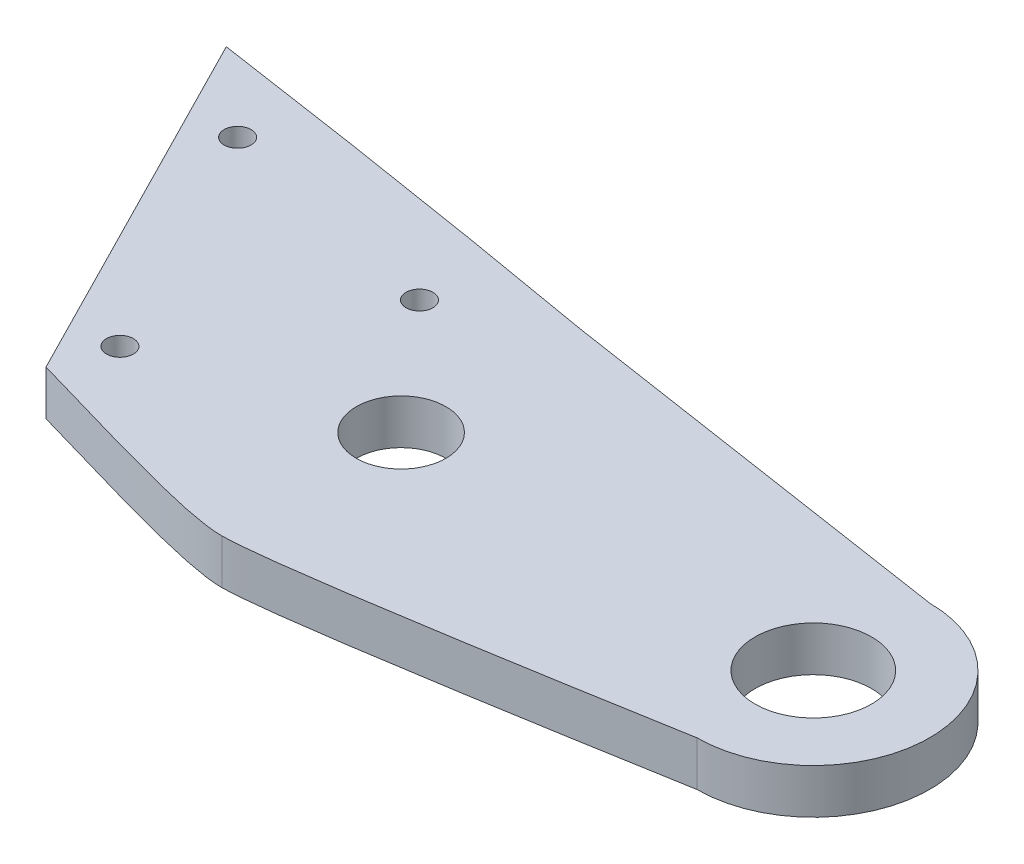
SolidWorks part; units mm, degrees
ref_plane "Front Plane" through (0, 0, 0) normal (0, 0, 1) x (1, 0, 0)
ref_plane "Top Plane" through (0, 0, 0) normal (0, 1, 0) x (1, 0, 0)
ref_plane "Right Plane" through (0, 0, 0) normal (1, 0, 0) x (0, 0, -1)
sketch "Sketch1" plane through (0, 0, 0) normal (0, 1, 0) x (1, 0, 0)
  line L0 (0, 0) -> (-300, 0) construction
  line L1 (0, 0) -> (46, 0) construction
  line L2 (-300, 0) -> (-300, 40) construction
  line L3 (-328.2843, 28.2843) -> (-271.7157, -28.2843) construction
  circle A0 centre (0, 0) radius 5
  circle A1 centre (46, 0) radius 6.5
  circle A2 centre (-300, 0) radius 40
  circle A3 centre (0, 0) radius 20
  circle A4 centre (46, 0) radius 13
  spline S0 degree 3 poles (-271.7157, -28.2843) (-189.2199, 54.2115) (-20, -20) (0, -20) knots 0 0 0 0 1 1 1 1
  spline S1 degree 3 poles (-328.2843, 28.2843) (-300, 56.5685) (-114.8731, 40.3783) (0, 20) knots 0 0 0 0 1 1 1 1
  spline S2 degree 2 poles (0, -20) (5.9085, -20) (46, -13) knots 0 0 0 1 1 1
  spline S3 degree 2 poles (0, 20) (0.0315, 20) (46, 13) knots 0 0 0 1 1 1
  dimension "D3" = 10
  dimension "D4" = 13
  dimension "D5" = 80
  dimension "D6" = 40
  dimension "D7" = 45
  dimension "D8" = 120
  dimension "D9" = 350
  dimension "D10" = 350
  dimension "D11" = 60
  dimension "D12" = 26
  dimension "D1" = 46
  dimension "D2" = 300
extrude "Boss-Extrude1" add sketch "Sketch1" along normal blind 20 and the other way blind 20 contours S1 A2 | S1 A2 S0 A3 | S3 A3 S0 A0 | S3 A3 S2 A4 | A4 A1 region at (-299.9271, 0, 0.2395) region at (-151.7179, 0, -19.1123) region at (-19.1932, 0, -3.0516) region at (26.0397, 0, 0.3418) region at (54.9324, 0, -8.9324)
ref_plane "Plane2" through (0, 20, 0) normal (0, 1, 0) x (1, 0, 0)
sketch "Sketch5" plane through (0, 20, 0) normal (0, 1, 0) x (1, 0, 0)
  line L0 (-47.037, 27.5275) -> (92.1208, 16.1646)
  line L1 (92.1208, 16.1646) -> (85.7247, -16.9188)
  line L2 (85.7247, -16.9188) -> (-17.2628, -30.9078)
  line L3 (-17.2628, -30.9078) -> (-47.037, 27.5275)
  line L4 (0, 0) -> (0, 89.1393) construction
  spline S0 degree 3 poles (-328.2843, 28.2843) (-300, 56.5685) (-114.8731, 40.3783) (0, 20) knots 0 0 0 0 1 1 1 1 construction
  point P7 (-52.7129, 28.3375)
  point P10 (-42.8155, -32.6838)
  point P11 (-62.9125, 29.7446)
  dimension "D1" = 27
  dimension "D2" = 54.5
extrude "Cut-Extrude4" cut sketch "Sketch5" against normal blind 35
sketch "Sketch6" plane through (0, -20, 0) normal (0, -1, 0) x (-1, 0, 0)
  circle A1 centre (24.0149, -7.3619) radius 1.5
  circle A2 centre (11.7743, 13.8231) radius 1.5
  circle A3 centre (37.6528, 19.404) radius 1.5
  dimension "D1" = 3
extrude "Cut-Extrude5" cut sketch "Sketch6" against normal blind 10
sketch "Sketch7" plane through (0, 20, 0) normal (0, 1, 0) x (1, 0, 0)
  line L0 (-47.037, 27.5275) -> (-26.1377, -13.4898)
  line L1 (-26.1377, -13.4898) -> (-379.5957, -92.5802)
  line L2 (-379.5957, -92.5802) -> (-321.5056, 137.2547)
  line L3 (-321.5056, 137.2547) -> (-47.037, 27.5275)
extrude "Cut-Extrude6" cut sketch "Sketch7" against normal blind 50
